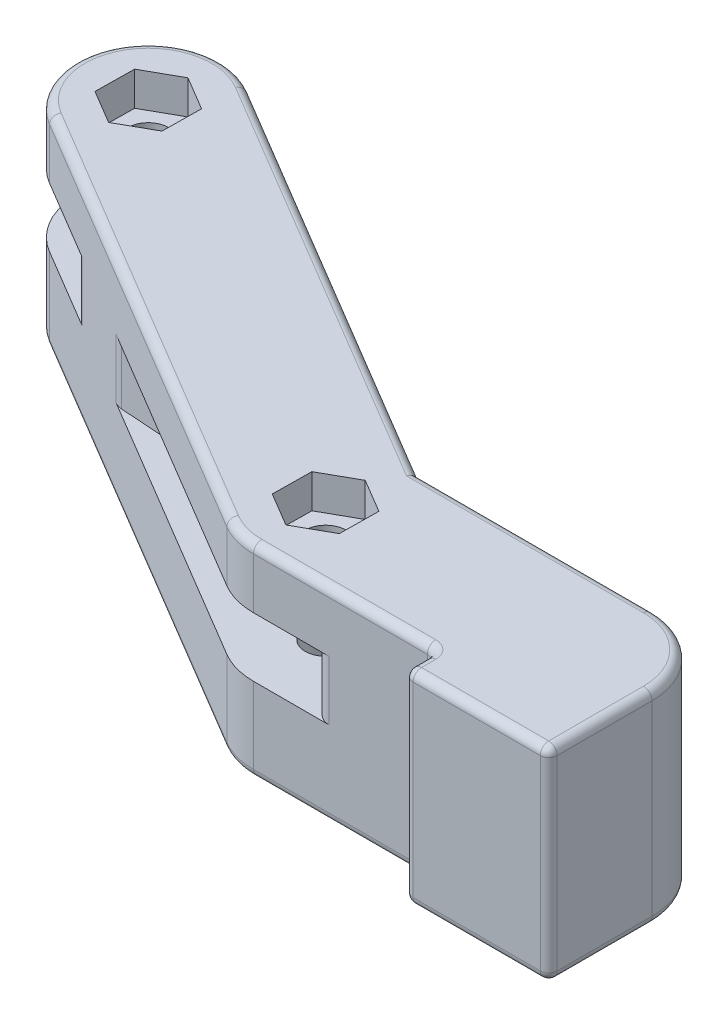
SolidWorks part; units mm, degrees
ref_plane "Front Plane" through (0, 0, 0) normal (0, 0, 1) x (1, 0, 0)
ref_plane "Top Plane" through (0, 0, 0) normal (0, 1, 0) x (1, 0, 0)
ref_plane "Right Plane" through (0, 0, 0) normal (1, 0, 0) x (0, 0, -1)
sketch "Sketch1" plane through (0, 0, 0) normal (0, 1, 0) x (1, 0, 0)
  line L0 (0, 0) -> (0, -15.7) construction
  line L1 (0, 0) -> (-20, -2.5) construction
  line L2 (-20, -2.5) -> (-20, -13.2) construction
  line L5 (-20, -13.2) -> (0, -15.7) construction
  line L6 (-20, -7.85) -> (0, -7.85) construction
  line L7 (-20, -2.5) -> (-0.8489, 13.5697) construction
  line L8 (0, 0) -> (24.9379, -1.7614) construction
  line L9 (-0.8489, 13.5697) -> (24.9379, -1.7614) construction
  line L10 (0, -7.85) -> (48.3923, -7.85) construction
  line L14 (1.323, 17.2228) -> (26.1058, 2.4886)
  line L15 (-3.0208, 9.9166) -> (22.766, -5.4145)
  line L16 (29.1879, -1.7614) -> (39.9379, -1.7614) construction
  line L17 (24.9379, -1.7614) -> (26.1379, -1.7614) construction
  line L18 (26.1058, 2.4886) -> (39.9379, 2.4886)
  line L19 (24.9379, -6.0114) -> (35.6879, -6.0114)
  line L21 (44.1879, -1.7614) -> (44.1879, -7.85)
  line L22 (35.6879, -6.0114) -> (35.6879, -7.85)
  line L23 (35.6879, -7.85) -> (44.1879, -7.85)
  arc A10 (1.323, 17.2228) -> (-3.0208, 9.9166) centre (-0.8489, 13.5697) ccw
  circle A16 centre (-0.8489, 13.5697) radius 1.2
  circle A17 centre (24.9379, -1.7614) radius 1.2
  arc A21 (44.1879, -1.7614) -> (39.9379, 2.4886) centre (39.9379, -1.7614) ccw
  arc A24 (22.766, -5.4145) -> (24.9379, -6.0114) centre (24.9379, -1.7614) ccw
  point P2 (24.9379, -2.6807)
  point P9 (12.0445, 5.9041)
  point P15 (32.4379, -1.7614)
  point P18 (29.1879, -7.85)
  point P27 (20.6879, -7.85)
  point P28 (39.9379, -2.6807)
  dimension "D4" = 25
  dimension "D5" = 25
  dimension "D16" = 2.4
  dimension "D17" = 1.8386
  dimension "D11" = 4.25
  dimension "D9" = 13.832
  dimension "D10" = 15
  dimension "D15" = 2.4
  dimension "D13" = 4.25
  dimension "D14" = 4.25
  dimension "D1" = 15.7
  dimension "D2" = 10.7
  dimension "D3" = 20
  dimension "D6" = 30
  dimension "D7" = 40
  dimension "D8" = 8.5
  dimension "D12" = 10.75
extrude "Boss-Extrude1" add sketch "Sketch1" along normal blind 12 contours L18 L14 A10 L15 A17 A16 region at (20.0094, 0, -3.1904)
ref_plane "Plane1" through (0, 6, 0) normal (0, 1, 0) x (1, 0, 0)
sketch "Sketch3" plane through (0, 6, 0) normal (0, 1, 0) x (1, 0, 0)
  line L0 (-20, -2.5) -> (-20, -13.2) construction
  line L1 (-20, -13.2) -> (0, -15.7) construction
  line L2 (0, -15.7) -> (0, 0) construction
  line L3 (0, 0) -> (-20, -2.5) construction
  line L4 (-20, -7.85) -> (0, -7.85) construction
  line L5 (-20, -2.5) -> (-0.8489, 13.5697) construction
  line L6 (24.9379, -1.7614) -> (0, 0) construction
  line L7 (-20, -2.5) -> (-0.8489, 13.5697) construction
  line L8 (-22.8925, 0.9472) -> (-3.7414, 17.0169)
  line L10 (0, 0) -> (24.9379, -1.7614) construction
  line L11 (0.3171, 4.4888) -> (25.2549, 2.7274)
  line L12 (-0.3171, -4.4888) -> (17.3396, -5.736)
  line L13 (-0.8489, 13.5697) -> (-13.6248, -7.9193) construction
  line L14 (3.0191, 11.27) -> (-1.0848, 4.3673)
  line L16 (24.9379, -1.7614) -> (12.1619, -23.2504) construction
  line L17 (28.8059, -4.0611) -> (16.03, -25.5501)
  line L19 (1.323, 17.2228) -> (26.1058, 2.4886) construction
  line L20 (17.3396, -5.736) -> (8.2939, -20.9507)
  line L21 (-4.355, -1.1332) -> (-9.7568, -10.2189)
  arc A0 (-22.8925, 0.9472) -> (-17.8859, -6.4725) centre (-20, -2.5) ccw
  arc A2 (0.3171, 4.4888) -> (-1.0848, 4.3673) centre (0, 0) ccw
  arc A4 (3.0191, 11.27) -> (-3.7414, 17.0169) centre (-0.8489, 13.5697) ccw
  arc A5 (-17.8859, -6.4725) -> (-9.7568, -10.2189) centre (-13.6248, -7.9193) ccw
  arc A6 (28.8059, -4.0611) -> (25.2549, 2.7274) centre (24.9379, -1.7614) ccw
  arc A7 (8.2939, -20.9507) -> (16.03, -25.5501) centre (12.1619, -23.2504) ccw
  arc A8 (-4.355, -1.1332) -> (-0.3171, -4.4888) centre (0, 0) ccw
  point P9 (-10.4244, 5.5348)
  point P15 (12.4689, -0.8807)
  point P22 (-7.2369, 2.8252)
  point P27 (18.5499, -12.5059)
  dimension "D1" = 20
  dimension "D2" = 10.7
  dimension "D3" = 15.7
  dimension "D4" = 25
  dimension "D5" = 25
  dimension "D6" = 9
  dimension "D10" = 25
  dimension "D11" = 25
extrude "Cut-Extrude1" cut sketch "Sketch3" against normal blind 1 and the other way blind 2.5
sketch "Sketch4" plane through (0, 12, 0) normal (0, 1, 0) x (1, 0, 0)
  line L0 (-0.8489, 13.5697) -> (24.9379, -1.7614) construction
  line L2 (22.9528, -0.5812) -> (22.9233, -2.8904)
  line L3 (22.9233, -2.8904) -> (24.9083, -4.0706)
  line L4 (24.9083, -4.0706) -> (26.9229, -2.9416)
  line L5 (26.9229, -2.9416) -> (26.9525, -0.6324)
  line L6 (26.9525, -0.6324) -> (24.9674, 0.5478)
  line L7 (24.9674, 0.5478) -> (22.9528, -0.5812)
  line L8 (1.1362, 12.3895) -> (1.1657, 14.6987)
  line L9 (1.1657, 14.6987) -> (-0.8193, 15.8789)
  line L10 (-0.8193, 15.8789) -> (-2.834, 14.7499)
  line L11 (-2.834, 14.7499) -> (-2.8635, 12.4407)
  line L12 (-2.8635, 12.4407) -> (-0.8784, 11.2605)
  line L13 (-0.8784, 11.2605) -> (1.1362, 12.3895)
  circle A0 centre (24.9379, -1.7614) radius 2 construction
  circle A1 centre (-0.8489, 13.5697) radius 2 construction
  dimension "D1" = 4
  dimension "D2" = 4
extrude "Cut-Extrude2" cut sketch "Sketch4" against normal blind 2
sketch "Sketch5" plane through (0, 0, 0) normal (0, -1, 0) x (1, 0, 0)
  circle A0 centre (-0.8489, -13.5697) radius 2.05
  circle A1 centre (24.9379, 1.7614) radius 2.05
  dimension "D1" = 4.1
  dimension "D2" = 4.1
extrude "Cut-Extrude3" cut sketch "Sketch5" against normal blind 2
fillet "Fillet1" radius 1 8 edges at (26.4169, 6.75, -2.4886) (27.6463, 6.75, 6.0114) (6.8894, 6.75, -4.0246) (0.8472, 6.75, -7.6169) (25.8385, 6.75, -2.6475) (2.5943, 6.75, -16.467) (24.9379, 0, -0.2886) (-0.8489, 0, -15.6197)
fillet "Fillet2" radius 0.5 23 edges at (35.6879, 12, 6.9307) (35.6879, 0, 6.9307) (44.1879, 0, 4.8057) (42.9431, 0, -1.2438) (13.7144, 0, -9.8557) (-4.502, 0, -15.7416) (9.8726, 0, -2.251) (23.8117, 0, 5.8595) (44.1879, 12, 4.8057) (33.0219, 12, -2.4886) (13.7144, 12, -9.8557) (-4.502, 12, -15.7416) (30.3129, 12, 6.0114) (23.8117, 12, 5.8595) (35.6879, 6, 7.85) (39.9379, 12, 7.85) (44.1879, 6, 7.85) (39.9379, 0, 7.85) (33.0219, 0, -2.4886) (30.3129, 0, 6.0114) (42.9431, 12, -1.2438) (9.8726, 12, -2.251) (35.6879, 6, 6.0114)
